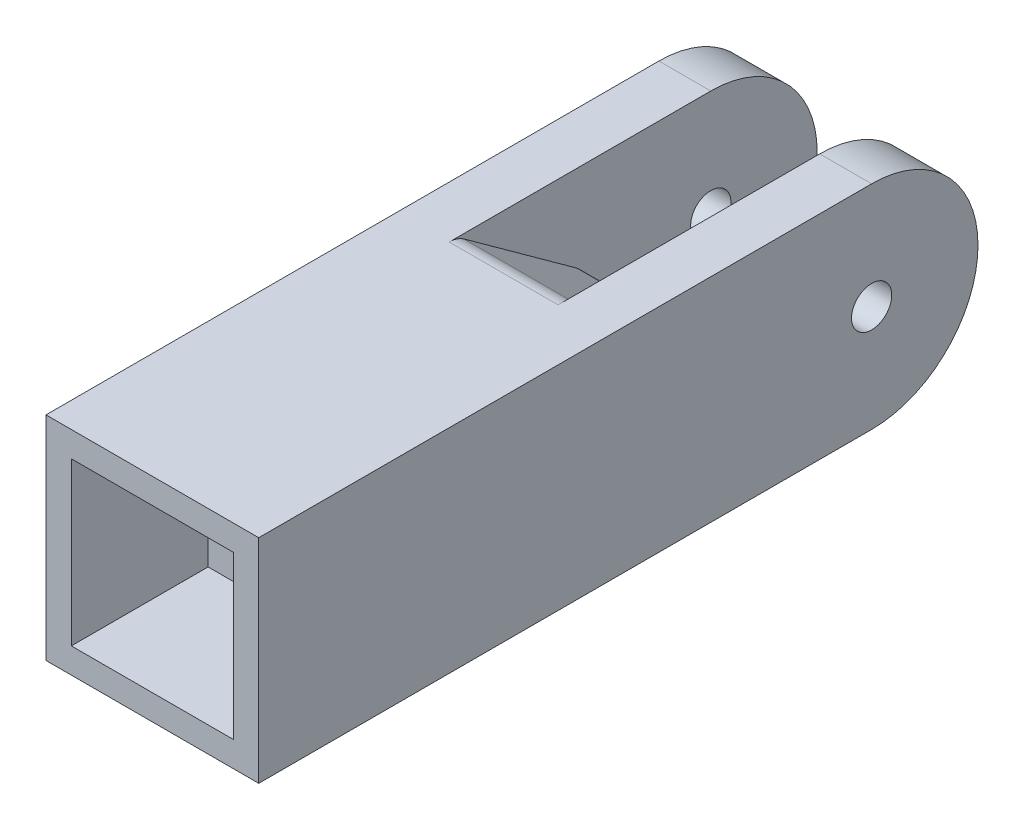
SolidWorks part; units mm, degrees
ref_plane "Front Plane" through (0, 0, 0) normal (0, 0, 1) x (1, 0, 0)
ref_plane "Top Plane" through (0, 0, 0) normal (0, 1, 0) x (1, 0, 0)
ref_plane "Right Plane" through (0, 0, 0) normal (1, 0, 0) x (0, 0, -1)
sketch "Sketch2" plane through (0, 0, 0) normal (0, 0, 1) x (1, 0, 0)
  line L1 (-21, 21) -> (21, 21)
  line L2 (-21, 21) -> (-21, -21)
  line L3 (-21, -21) -> (21, -21)
  line L4 (21, 21) -> (21, -21)
  line L5 (-21, 21) -> (21, -21) construction
  line L6 (-21, -21) -> (21, 21) construction
  point P0 (0, 0)
  dimension "D1" = 42
  dimension "D2" = 42
extrude "Boss-Extrude1" add sketch "Sketch2" along normal blind 100
ref_plane "Plane1" through (0, 0, 0) normal (0, 0, -1) x (-1, 0, 0)
sketch "Sketch3" plane through (0, 0, 0) normal (0, 0, -1) x (-1, 0, 0)
  line L0 (-21, 21) -> (21, 21) construction
  line L1 (21, -21) -> (10.75, -21)
  line L2 (21, -21) -> (21, 21)
  line L3 (21, 21) -> (10.75, 21)
  line L4 (10.75, -21) -> (10.75, 21)
  line L6 (-21, -21) -> (-10.75, -21)
  line L7 (-21, -21) -> (-21, 21)
  line L8 (-21, 21) -> (-10.75, 21)
  line L9 (-10.75, -21) -> (-10.75, 21)
  dimension "D1" = 10.25
  dimension "D2" = 10.25
extrude "Boss-Extrude2" add sketch "Sketch3" along normal blind 21
ref_plane "Plane2" through (-21, 0, 0) normal (-1, 0, 0) x (0, 0, 1)
sketch "Sketch4" plane through (-21, 0, 0) normal (-1, 0, 0) x (0, 0, 1)
  line L0 (-21, -21) -> (-21, 21)
  arc A0 (-21, -21) -> (-21, 21) centre (-21, 0) cw
  dimension "D1" = 21
extrude "Boss-Extrude3" add sketch "Sketch4" against normal blind 10.25
ref_plane "Plane3" through (21, 0, 0) normal (1, 0, 0) x (0, 0, -1)
sketch "Sketch5" plane through (21, 0, 0) normal (1, 0, 0) x (0, 0, -1)
  line L0 (21, 21) -> (21, -21)
  arc A0 (21, 21) -> (21, -21) centre (21, 0) cw
  dimension "D1" = 21
extrude "Boss-Extrude4" add sketch "Sketch5" against normal blind 10.25
ref_plane "Plane4" through (0, 0, 100) normal (0, 0, 1) x (1, 0, 0)
sketch "Sketch6" plane through (0, 0, 100) normal (0, 0, 1) x (1, 0, 0)
  line L0 (21, 21) -> (-21, 21) construction
  line L1 (-16, 16) -> (16, 16)
  line L2 (-16, 16) -> (-16, -16)
  line L3 (-16, -16) -> (16, -16)
  line L4 (16, 16) -> (16, -16)
  line L5 (-16, 16) -> (16, -16) construction
  line L6 (-16, -16) -> (16, 16) construction
  line L7 (21, -21) -> (21, 21) construction
  point P0 (0, 0)
  dimension "D1" = 5
  dimension "D2" = 5
extrude "Cut-Extrude1" cut sketch "Sketch6" against normal blind 27
ref_plane "Plane5" through (10.75, 0, 0) normal (-1, 0, 0) x (0, 0, 1)
sketch "Sketch7" plane through (10.75, 0, 0) normal (-1, 0, 0) x (0, 0, 1)
  line L0 (0, -21) -> (0, 21) construction
  circle A0 centre (-21, 0) radius 3.975
  dimension "D2" = 7.95
  dimension "D1" = 21
extrude "Cut-Extrude2" cut sketch "Sketch7" against normal through all
ref_plane "Plane6" through (-10.75, 0, 0) normal (1, 0, 0) x (0, 0, -1)
sketch "Sketch9" plane through (-10.75, 0, 0) normal (1, 0, 0) x (0, 0, -1)
  line L0 (0, 21) -> (0, -21) construction
  circle A0 centre (21, 0) radius 3.975
  dimension "D2" = 7.95
  dimension "D1" = 21
extrude "Cut-Extrude3" cut sketch "Sketch9" against normal through all
ref_plane "Plane9" through (10.75, 0, 0) normal (-1, 0, 0) x (0, 0, 1)
sketch "Sketch11" plane through (10.75, 0, 0) normal (-1, 0, 0) x (0, 0, 1)
  line L0 (0, 0) -> (0, 21)
  line L1 (0, 0) -> (0, -21)
  line L2 (0, -21) -> (29.0252, -21)
  line L3 (29.0252, -21) -> (0, 0)
  line L4 (0, -21) -> (0, 21) construction
  line L5 (0, 21) -> (29.0252, 21) construction
  line L6 (29.0252, 21) -> (0, 0) construction
  line L7 (0, 0) -> (0, 21)
  line L8 (0, 0) -> (29.0252, 21)
  line L9 (29.0252, 21) -> (0, 21)
  point P3 (0, 0)
  point P5 (0, 0)
  line M5 (0, -21) -> (0, 21)
extrude "Cut-Extrude5" cut sketch "Sketch11" along normal blind 21.5 contours L8 L9 M5 | L1 L2 L3 region at (10.75, 14, 9.6751)
fillet "Fillet1" radius 5 1 edges at (0, 0, 0)
fillet "Fillet2" radius 5 1 edges at (0, -21, 29.0252)
fillet "Fillet3" radius 5 1 edges at (0, 21, 29.0252)
